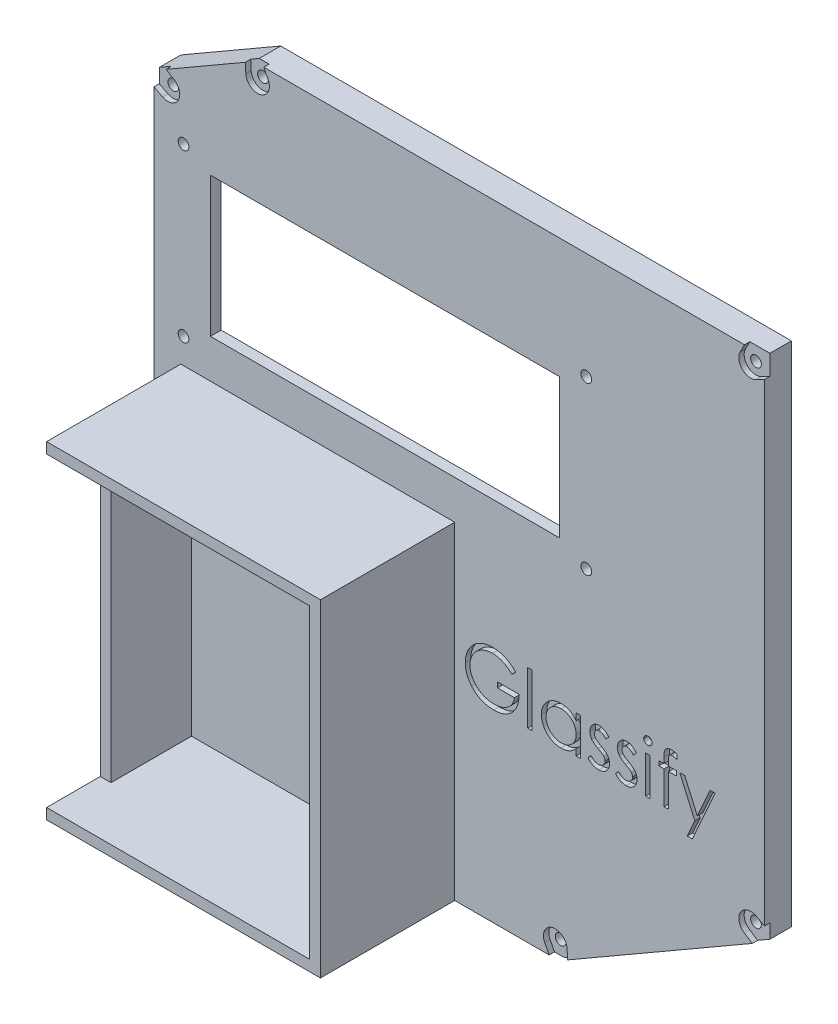
SolidWorks part; units mm, degrees
ref_plane "Front Plane" through (0, 0, 0) normal (0, 0, 1) x (1, 0, 0)
ref_plane "Top Plane" through (0, 0, 0) normal (0, 1, 0) x (1, 0, 0)
ref_plane "Right Plane" through (0, 0, 0) normal (1, 0, 0) x (0, 0, -1)
sketch "Sketch1" plane through (0, 0, 0) normal (0, 0, 1) x (1, 0, 0)
  line L6 (62.1, 287.25) -> (-33, 287.25)
  line L7 (62.1, 192.75) -> (62.1, 287.25)
  line L8 (23.8217, 170.65) -> (62.1, 192.75)
  line L9 (-51.6, 170.65) -> (23.8217, 170.65)
  line L10 (-51.6, 276.5113) -> (-51.6, 170.65)
  line L11 (-33, 287.25) -> (-51.6, 276.5113)
  line L18 (62.1, 287.25) -> (-33, 287.25)
  line L19 (62.1, 192.75) -> (62.1, 287.25)
  line L20 (23.8217, 170.65) -> (62.1, 192.75)
  line L21 (-51.6, 170.65) -> (23.8217, 170.65)
  line L22 (-51.6, 276.5113) -> (-51.6, 170.65)
  line L23 (-33, 287.25) -> (-51.6, 276.5113)
  line L24 (-50, 273.0506) -> (-50, 175.2096)
  line L25 (-34.5004, 284.5362) -> (-47.8029, 276.856)
  line L26 (57.5404, 285.65) -> (-30.3437, 285.65)
  line L27 (60.5, 196.2107) -> (60.5, 282.6904)
  line L28 (25.3221, 173.3638) -> (58.3029, 192.4053)
  line L29 (-47.0404, 172.25) -> (21.1654, 172.25)
  line L30 (-50, 273.0506) -> (-50, 175.2096)
  line L31 (-34.5004, 284.5362) -> (-47.8029, 276.856)
  line L32 (57.5404, 285.65) -> (-30.3437, 285.65)
  line L33 (60.5, 196.2107) -> (60.5, 282.6904)
  line L34 (25.3221, 173.3638) -> (58.3029, 192.4053)
  line L35 (-47.0404, 172.25) -> (21.1654, 172.25)
  circle A1 centre (-49, 173.25) radius 1
  circle A2 centre (-49, 173.25) radius 1
  circle A3 centre (-49, 275.0102) radius 1
  circle A4 centre (-49, 275.0102) radius 1
  circle A5 centre (-32.3033, 284.65) radius 1
  circle A6 centre (-32.3033, 284.65) radius 1
  circle A7 centre (59.5, 194.2511) radius 1
  circle A8 centre (59.5, 194.2511) radius 1
  circle A9 centre (59.5, 284.65) radius 1
  circle A10 centre (59.5, 284.65) radius 1
  circle A11 centre (23.125, 173.25) radius 1
  circle A12 centre (23.125, 173.25) radius 1
  arc A18 (-47.0404, 172.25) -> (-50, 175.2096) centre (-49, 173.25) ccw
  arc A19 (-50, 273.0506) -> (-47.8029, 276.856) centre (-49, 275.0102) ccw
  arc A20 (-34.5004, 284.5362) -> (-30.3437, 285.65) centre (-32.3033, 284.65) ccw
  arc A21 (57.5404, 285.65) -> (60.5, 282.6904) centre (59.5, 284.65) ccw
  arc A22 (60.5, 196.2107) -> (58.3029, 192.4053) centre (59.5, 194.2511) ccw
  arc A23 (25.3221, 173.3638) -> (21.1654, 172.25) centre (23.125, 173.25) ccw
  arc A24 (-47.0404, 172.25) -> (-50, 175.2096) centre (-49, 173.25) ccw
  arc A25 (-50, 273.0506) -> (-47.8029, 276.856) centre (-49, 275.0102) ccw
  arc A26 (-34.5004, 284.5362) -> (-30.3437, 285.65) centre (-32.3033, 284.65) ccw
  arc A27 (57.5404, 285.65) -> (60.5, 282.6904) centre (59.5, 284.65) ccw
  arc A28 (60.5, 196.2107) -> (58.3029, 192.4053) centre (59.5, 194.2511) ccw
  arc A29 (25.3221, 173.3638) -> (21.1654, 172.25) centre (23.125, 173.25) ccw
  dimension "D1" = 0
  dimension "D2" = 0
  dimension "D3" = 0
  dimension "D4" = 0
  dimension "D5" = 0
  dimension "D6" = 0
  dimension "D7" = 0
  dimension "D8" = 0
extrude "Boss-Extrude1" add sketch "Sketch1" along normal blind 3
sketch "Sketch2" plane through (0, 0, 3) normal (0, 0, 1) x (1, 0, 0)
  line L0 (23.8217, 170.65) -> (62.1, 192.75) construction
  line L1 (-51.6, 170.65) -> (23.8217, 170.65) construction
  line L2 (-51.6, 276.5113) -> (-51.6, 170.65) construction
  line L3 (-33, 287.25) -> (-51.6, 276.5113) construction
  line L4 (62.1, 287.25) -> (-33, 287.25) construction
  line L5 (62.1, 192.75) -> (62.1, 287.25) construction
  line L6 (23.8217, 170.65) -> (62.1, 192.75)
  line L7 (-51.6, 170.65) -> (23.8217, 170.65)
  line L8 (-51.6, 276.5113) -> (-51.6, 170.65)
  line L9 (-33, 287.25) -> (-51.6, 276.5113)
  line L10 (62.1, 287.25) -> (-33, 287.25)
  line L11 (62.1, 192.75) -> (62.1, 287.25)
extrude "Boss-Extrude2" add sketch "Sketch2" along normal blind 2
sketch "Sketch3" plane through (0, 0, 5) normal (0, 0, 1) x (1, 0, 0)
  line L1 (-48.6, 269.8843) -> (31.4, 269.8843) construction
  line L2 (-48.6, 269.8843) -> (-48.6, 233.8843) construction
  line L3 (-48.6, 233.8843) -> (31.4, 233.8843) construction
  line L4 (31.4, 269.8843) -> (31.4, 233.8843) construction
  line L5 (-51.6, 170.65) -> (23.8217, 170.65) construction
  line L6 (-48.6, 228.65) -> (-3.6, 228.65) construction
  line L7 (-48.6, 228.65) -> (-48.6, 173.65) construction
  line L8 (-48.6, 173.65) -> (-3.6, 173.65) construction
  line L9 (-3.6, 228.65) -> (-3.6, 173.65) construction
  line L10 (-51.6, 276.5113) -> (-51.6, 170.65) construction
  point P4 (8.7324, 218.75)
  point P5 (-1.1582, 231.2804)
  point P6 (41.918, 280.4244)
  point P7 (33.7221, 275.4356)
  point P8 (-46.2174, 272.4661)
  point P9 (-46.4549, 175.6597)
  point P18 (31.4, 232.6479)
  point P19 (31.4, 233.8843)
  point P20 (0, 0)
  dimension "D1" = 80
  dimension "D2" = 36
  dimension "D3" = 55
  dimension "D4" = 45
  dimension "D5" = 3
  dimension "D6" = 3
sketch "Sketch4" plane through (0, 0, 3) normal (0, 0, -1) x (-1, 0, 0)
  line L0 (48.6, 269.8843) -> (-31.4, 269.8843) construction
  line L1 (-23.9, 264.8843) -> (41.1, 264.8843)
  line L2 (-23.9, 264.8843) -> (-23.9, 238.8843)
  line L3 (-23.9, 238.8843) -> (41.1, 238.8843)
  line L4 (41.1, 264.8843) -> (41.1, 238.8843)
  line L5 (48.6, 233.8843) -> (-31.4, 233.8843) construction
  line L6 (48.6, 269.8843) -> (48.6, 233.8843) construction
  line L7 (-31.4, 269.8843) -> (-31.4, 233.8843) construction
  dimension "D1" = 5
  dimension "D2" = 5
  dimension "D3" = 7.5
  dimension "D4" = 7.5
extrude "Cut-Extrude1" cut sketch "Sketch4" against normal up to surface (2 mm away) up to face at (1.9703, 230.8435, 5)
sketch "Sketch5" plane through (0, 0, 3) normal (0, 0, -1) x (-1, 0, 0)
  line L0 (48.6, 269.8843) -> (48.6, 233.8843) construction
  line L1 (-31.4, 269.8843) -> (-31.4, 233.8843) construction
  line L2 (48.6, 269.8843) -> (-31.4, 269.8843) construction
  line L3 (48.6, 233.8843) -> (-31.4, 233.8843) construction
  line L4 (48.6, 228.65) -> (3.6, 228.65) construction
  line L5 (48.6, 228.65) -> (48.6, 173.65) construction
  line L6 (48.6, 173.65) -> (3.6, 173.65) construction
  line L7 (3.6, 228.65) -> (3.6, 173.65) construction
  line L8 (48.6, 228.65) -> (3.6, 228.65) construction
  line L9 (48.6, 228.65) -> (48.6, 173.65) construction
  line L10 (48.6, 173.65) -> (3.6, 173.65) construction
  line L11 (3.6, 228.65) -> (3.6, 173.65) construction
  line L13 (6.1, 226.15) -> (31.1, 226.15)
  line L14 (6.1, 226.15) -> (6.1, 224.15)
  line L15 (6.1, 224.15) -> (31.1, 224.15)
  line L16 (31.1, 226.15) -> (31.1, 224.15)
  circle A0 centre (46.1, 267.3843) radius 1
  circle A1 centre (46.1, 236.3843) radius 1
  circle A2 centre (-28.9, 267.3843) radius 1
  circle A3 centre (-28.9, 236.3843) radius 1
  dimension "D5" = 2
  dimension "D1" = 2.5
  dimension "D2" = 2.5
  dimension "D3" = 2.5
  dimension "D4" = 2.5
  dimension "D6" = 25
  dimension "D7" = 2
  dimension "D8" = 2.5
  dimension "D9" = 2.5
extrude "Cut-Extrude2" cut sketch "Sketch5" against normal up to surface (2 mm away) up to face at (-8.6, 251.8843, 5)
sketch "Sketch6" plane through (0, 0, 5) normal (0, 0, 1) x (1, 0, 0)
  line L0 (-51.6, 170.65) -> (23.8217, 170.65) construction
  line L2 (-51.6, 276.5113) -> (-51.6, 170.65) construction
  line L4 (-43.6, 173.65) -> (1.4, 173.65) construction
  line L5 (1.4, 228.65) -> (1.4, 173.65) construction
  line L6 (-43.6, 228.65) -> (1.4, 228.65) construction
  line L7 (-43.6, 228.65) -> (-43.6, 173.65) construction
  line L8 (-44.6, 172.65) -> (2.4, 172.65)
  line L9 (2.4, 229.65) -> (2.4, 172.65)
  line L10 (-44.6, 229.65) -> (2.4, 229.65)
  line L11 (-44.6, 229.65) -> (-44.6, 172.65)
  line L12 (-46.6, 231.65) -> (4.4, 231.65)
  line L13 (4.4, 231.65) -> (4.4, 170.65)
  line L14 (-46.6, 170.65) -> (4.4, 170.65)
  line L15 (-46.6, 231.65) -> (-46.6, 170.65)
  point P12 (0, 0)
  point P13 (0, 0)
  point P16 (-2.332, 230.6625)
  dimension "D3" = 45
  dimension "D4" = 55
  dimension "D5" = 5
  dimension "D1" = 1
  dimension "D2" = 2
extrude "Boss-Extrude3" add sketch "Sketch6" along normal blind 25
sketch "Sketch7" plane through (-51.6, 0, 0) normal (-1, 0, 0) x (0, 0, 1)
  line L0 (30, 172.65) -> (30, 229.65) construction
  line L1 (30, 172.65) -> (30, 229.65)
  line L2 (30, 229.65) -> (20, 229.65)
  line L3 (20, 229.65) -> (20, 172.65)
  line L4 (20, 172.65) -> (30, 172.65)
  dimension "D1" = 10
extrude "Cut-Extrude3" cut sketch "Sketch7" against normal blind 25
sketch "Sketch8" plane through (0, 0, 5) normal (0, 0, 1) x (1, 0, 0)
  line L0 (60.5, 196.2107) -> (62.1, 195.3942)
  line L1 (62.1, 192.75) -> (62.1, 287.25) construction
  line L2 (62.1, 195.3942) -> (62.1, 192.75)
  line L3 (62.1, 192.75) -> (59.8101, 191.4279)
  line L4 (23.8217, 170.65) -> (62.1, 192.75) construction
  line L5 (59.8101, 191.4279) -> (58.3029, 192.4053)
  line L6 (25.3221, 173.3638) -> (25.415, 171.5699)
  line L7 (25.415, 171.5699) -> (23.8217, 170.65)
  line L8 (23.8217, 170.65) -> (21.9819, 170.65)
  line L9 (4.4, 170.65) -> (23.8217, 170.65) construction
  line L10 (21.9819, 170.65) -> (21.1654, 172.25)
  line L11 (-47.0404, 172.25) -> (-47.8569, 170.65)
  line L18 (-47.0404, 172.25) -> (21.1654, 172.25)
  line L19 (-50, 273.0506) -> (-50, 175.2096)
  line L20 (-34.5004, 284.5362) -> (-47.8029, 276.856)
  line L21 (57.5404, 285.65) -> (-30.3437, 285.65)
  line L22 (60.5, 196.2107) -> (60.5, 282.6904)
  line L23 (25.3221, 173.3638) -> (58.3029, 192.4053)
  line L30 (-51.6, 170.65) -> (23.8217, 170.65) construction
  line L31 (-47.8569, 170.65) -> (-51.6, 170.65)
  line L32 (-51.6, 170.65) -> (-51.6, 174.3931)
  line L33 (-51.6, 276.5113) -> (-51.6, 170.65) construction
  line L34 (-51.6, 174.3931) -> (-50, 175.2096)
  line L35 (-47.8029, 276.856) -> (-49.3101, 277.8334)
  line L36 (-33, 287.25) -> (-51.6, 276.5113) construction
  line L37 (-49.3101, 277.8334) -> (-51.6, 276.5113)
  line L38 (-51.6, 276.5113) -> (-51.6, 273.8671)
  line L39 (-51.6, 276.5113) -> (-51.6, 170.65) construction
  line L40 (-51.6, 273.8671) -> (-50, 273.0506)
  line L41 (-30.3437, 285.65) -> (-31.1602, 287.25)
  line L42 (62.1, 287.25) -> (-33, 287.25) construction
  line L43 (-31.1602, 287.25) -> (-33, 287.25)
  line L44 (-33, 287.25) -> (-34.5933, 286.3301)
  line L45 (-51.6, 276.5113) -> (-33, 287.25) construction
  line L46 (-34.5933, 286.3301) -> (-34.5004, 284.5362)
  line L47 (57.5404, 285.65) -> (58.3569, 287.25)
  line L48 (58.3569, 287.25) -> (62.1, 287.25)
  line L49 (62.1, 287.25) -> (62.1, 283.5069)
  line L50 (62.1, 283.5069) -> (60.5, 282.6904)
  circle A1 centre (-49, 275.0102) radius 1
  circle A2 centre (-49, 275.0102) radius 1
  circle A3 centre (-49, 173.25) radius 1
  circle A4 centre (-49, 173.25) radius 1
  circle A5 centre (23.125, 173.25) radius 1
  circle A6 centre (23.125, 173.25) radius 1
  circle A7 centre (59.5, 284.65) radius 1
  circle A8 centre (59.5, 284.65) radius 1
  circle A9 centre (59.5, 194.2511) radius 1
  circle A10 centre (59.5, 194.2511) radius 1
  circle A11 centre (-32.3033, 284.65) radius 1
  circle A12 centre (-32.3033, 284.65) radius 1
  arc A18 (-47.0404, 172.25) -> (-50, 175.2096) centre (-49, 173.25) ccw
  arc A19 (-50, 273.0506) -> (-47.8029, 276.856) centre (-49, 275.0102) ccw
  arc A20 (-34.5004, 284.5362) -> (-30.3437, 285.65) centre (-32.3033, 284.65) ccw
  arc A21 (57.5404, 285.65) -> (60.5, 282.6904) centre (59.5, 284.65) ccw
  arc A22 (60.5, 196.2107) -> (58.3029, 192.4053) centre (59.5, 194.2511) ccw
  arc A23 (25.3221, 173.3638) -> (21.1654, 172.25) centre (23.125, 173.25) ccw
  arc A24 (-47.0404, 172.25) -> (-50, 175.2096) centre (-49, 173.25) ccw
  arc A25 (-50, 273.0506) -> (-47.8029, 276.856) centre (-49, 275.0102) ccw
  arc A26 (-34.5004, 284.5362) -> (-30.3437, 285.65) centre (-32.3033, 284.65) ccw
  arc A27 (57.5404, 285.65) -> (60.5, 282.6904) centre (59.5, 284.65) ccw
  arc A28 (60.5, 196.2107) -> (58.3029, 192.4053) centre (59.5, 194.2511) ccw
  arc A29 (25.3221, 173.3638) -> (21.1654, 172.25) centre (23.125, 173.25) ccw
  text T0 "Glassify" font "Century Gothic" height in points 36
  dimension "D1" = 0
  dimension "D2" = 0
  dimension "D4" = 0
  dimension "D5" = 0
  dimension "D6" = 0
  dimension "D7" = 0
  dimension "D8" = 0
extrude "Cut-Extrude4" cut sketch "Sketch8" against normal blind 1
extrude "Cut-Extrude5" cut sketch "Sketch8<2>" against normal through all both and the other way through all contours A4 | A10 | A6 | A2 | A12 | A8 region at (-49, 173.25, 5)
sketch "Sketch8<2>" plane through (0, 0, 5) normal (0, 0, 1) x (1, 0, 0) same geometry as "Sketch8"
